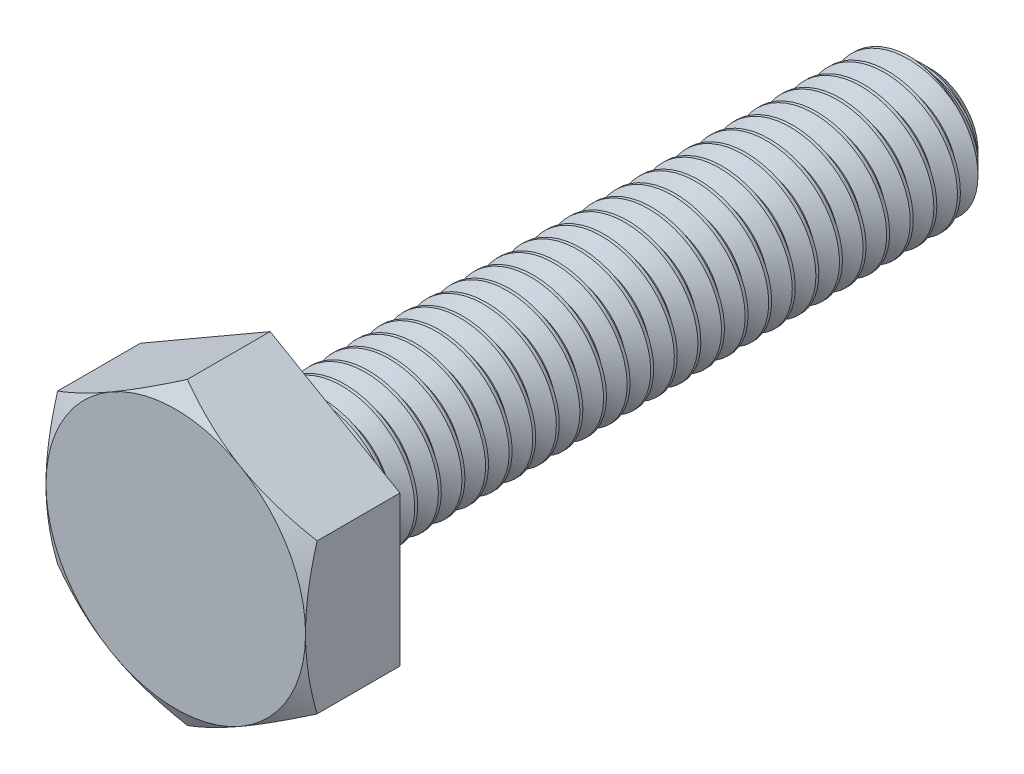
SolidWorks part; units mm, degrees
note: '?' marks a value the reader was unsure of.
ref_plane "Front Plane" through (0, 0, 0) normal (0, 0, 1) x (1, 0, 0)
ref_plane "Top Plane" through (0, 0, 0) normal (0, 1, 0) x (1, 0, 0)
ref_plane "Right Plane" through (0, 0, 0) normal (1, 0, 0) x (0, 0, -1)
sketch "Sketch1" plane through (0, 0, 0) normal (1, 0, 0) x (0, 0, -1)
  line L0 (-7, 0) -> (0, 0) construction
  line L1 (0, 0) -> (7, 0) construction
  line L2 (-7, 0) -> (-9, 0) construction
  line L3 (-7, 0) -> (-7, 1.5) construction
  line L4 (-7, 1.5) -> (-7, 2.75) construction
  line L5 (-7, 0) -> (-7, -1.5) construction
  line L6 (-7, -1.5) -> (-7, -2.75) construction
  line L7 (7, 0) -> (7, 2.75) construction
  line L8 (7, 2.75) -> (-7, 2.75) construction
  line L9 (-7, 0) -> (-7, 2.75) construction
  line L10 (-9, 0) -> (-9, 2.75) construction
  line L11 (-9, 2.75) -> (-7, 2.75) construction
  line L12 (-9, 0) -> (-9, -2.75) construction
  line L13 (-9, -2.75) -> (-7, -2.75) construction
  line L14 (7, 0) -> (7, -2.75) construction
  line L15 (7, -2.75) -> (-7, -2.75) construction
  line L16 (-7, 0) -> (-7, -2.75) construction
  line L17 (-7, 1.5) -> (7, 1.5) construction
  line L18 (-7, -1.5) -> (7, -1.5) construction
  line L19 (6.9687, 1.5541) -> (7.2187, 1.1211) construction
  line L20 (7.2187, 1.1211) -> (7.4687, 1.5541) construction
  line L21 (7.4687, 1.5541) -> (6.9687, 1.5541) construction
  line L22 (7.2187, 1.5541) -> (7.2187, 1.5) construction
  line L23 (7.2187, 1.5) -> (7.2187, 1.1752) construction
  line L24 (7.2187, 1.1752) -> (7.2187, 1.1211) construction
  line L25 (7.2187, 1.5271) -> (7.4531, 1.5271) construction
  line L26 (7.2187, 1.5271) -> (6.9844, 1.5271) construction
  line L27 (7.2187, 1.5) -> (7.4375, 1.5) construction
  line L28 (7.1875, 1.1752) -> (7.25, 1.1752) construction
  line L29 (7.1875, 1.1752) -> (6.9844, 1.5271)
  line L30 (6.9844, 1.5271) -> (7.4531, 1.5271)
  line L31 (7.4531, 1.5271) -> (7.25, 1.1752)
  line L32 (7.25, 1.1752) -> (7.1875, 1.1752)
  line L33 (7.2187, 1.5) -> (7, 1.5) construction
  point P10 (-7, 0)
  point P18 (3.25, -1.5)
  dimension "D2" = 0.0625
  dimension "D1" = 3.75
ref_plane "Plane1" through (0, 0, 7) normal (0, 0, 1) x (1, 0, 0)
sketch "Sketch2" plane through (0, 0, 7) normal (0, 0, 1) x (1, 0, 0)
  circle A0 centre (0, 0) radius 1.5
extrude "Boss-Extrude1" add sketch "Sketch2" against normal up to vertex (14 mm away) up to point (0, 0, -7)
sketch "Sketch3" plane through (0, 0, 7) normal (0, 0, 1) x (1, 0, 0)
  line L1 (0, 3.1754) -> (-2.75, 1.5877)
  line L2 (-2.75, 1.5877) -> (-2.75, -1.5877)
  line L3 (-2.75, -1.5877) -> (0, -3.1754)
  line L4 (0, -3.1754) -> (2.75, -1.5877)
  line L5 (2.75, -1.5877) -> (2.75, 1.5877)
  line L6 (2.75, 1.5877) -> (0, 3.1754)
  circle A0 centre (0, 0) radius 2.75 construction
extrude "Boss-Extrude2" add sketch "Sketch3" along normal up to vertex (2 mm away) separate body up to point (0, 0, 9)
sketch "Sketch4" plane through (0, 0, 9) normal (0, 0, 1) x (1, 0, 0)
  circle A0 centre (0, 0) radius 2.75 construction
  circle A1 centre (0, 0) radius 2.75
extrude "Cut-Extrude1" cut sketch "Sketch4" against normal through all draft 60 flip side to cut
chamfer "Chamfer1" distance 0.5 angle 45 1 edges at (1.5, 0, -7)
sketch "Sketch6" plane through (0, 0, -7) normal (0, 0, -1) x (-1, 0, 0)
  circle A1 centre (0, 0) radius 1
  circle A3 centre (0, 0) radius 1
  dimension "D1" = 0
curve "Helix/Spiral1" pitch 0.5 height 14.5 turns 29
sketch "Sketch7" plane through (0, 0, 9) normal (0, 0, -1) x (-1, 0, 0)
  circle A2 centre (0, 0) radius 1.5 construction
  circle A3 centre (0, 0) radius 1.5
sketch "Sketch8" plane through (0, 0, 0) normal (1, 0, 0) x (0, 0, -1)
  line L0 (6.9844, 1.5271) -> (7.4531, 1.5271) construction
  line L1 (7.1875, 1.1752) -> (6.9844, 1.5271) construction
  line L2 (7.25, 1.1752) -> (7.1875, 1.1752) construction
  line L3 (7.4531, 1.5271) -> (7.25, 1.1752) construction
  line L4 (6.9844, 1.5271) -> (7.4531, 1.5271)
  line L5 (7.1875, 1.1752) -> (6.9844, 1.5271)
  line L6 (7.25, 1.1752) -> (7.1875, 1.1752)
  line L7 (7.4531, 1.5271) -> (7.25, 1.1752)
sweep "Cut-Sweep2" cut profiles "Sketch8" path "Helix/Spiral1" align with end faces yes
extrude "Boss-Extrude5" add sketch "Sketch7" along normal up to vertex
ref_axis "Center Axis 1" through (0, 0, 8.215) along (0, 0, 1)?
ref_plane "Contact Plane 1" through (0, 0, 7) normal (0, 0, -1) x (-1, 0, 0)
equation "\"D2@Sketch1\" = \"Pitch@Sketch1\" / 8"
equation "\"D4@Helix/Spiral1\"=\"Pitch@Sketch1\""
equation "\"D3@Helix/Spiral1\"=\"Thread Length@Sketch1\"+\"Pitch@Sketch1\""
equation "\"D1@Chamfer1\"=\"Pitch@Sketch1\""
equation "\"D1@Sketch1\"=\"Pitch@Sketch1\"*7.5"
